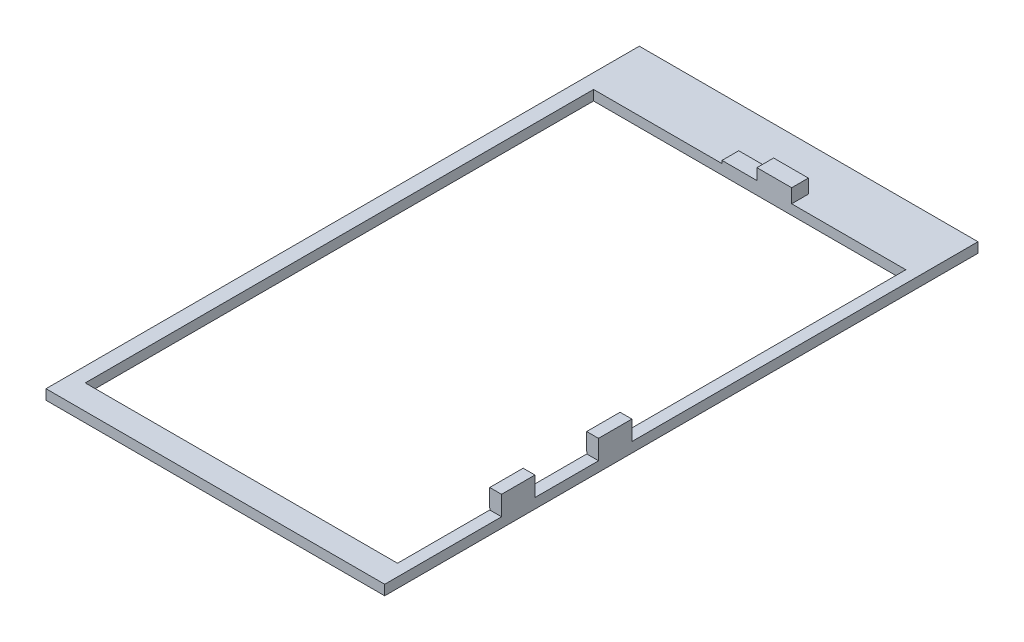
SolidWorks part; units mm, degrees
ref_plane "Front Plane" through (0, 0, 0) normal (0, 0, 1) x (1, 0, 0)
ref_plane "Top Plane" through (0, 0, 0) normal (0, 1, 0) x (1, 0, 0)
ref_plane "Right Plane" through (0, 0, 0) normal (1, 0, 0) x (0, 0, -1)
sketch "Sketch1" plane through (0, 0, 0) normal (0, 1, 0) x (1, 0, 0)
  line L0 (26.2481, 14.4067) -> (26.2382, 20.9067) construction
  line L1 (4.7511, 20.874) -> (16.7382, 20.8922) construction
  line L2 (-0.3474, -87.1339) -> (-0.3459, -88.1339) construction
  line L3 (26.2481, 14.4067) -> (16.7481, 14.3922) construction
  line L4 (26.2481, 14.4067) -> (-0.0019, 14.3667) construction
  line L5 (24.2864, -1.2339) -> (28.4864, -1.2339) construction
  line L6 (26.4026, -87.0932) -> (-27.0974, -87.1746) construction
  line L7 (-27.0974, -87.1746) -> (-27.2518, 14.3252) construction
  line L8 (-27.2518, 14.3252) -> (-0.0019, 14.3667) construction
  line L9 (16.7481, 14.3922) -> (16.7382, 20.8922) construction
  line L10 (4.7614, 14.1135) -> (4.7511, 20.874) construction
  line L16 (-0.3459, -88.1339) -> (29.1041, -88.1339)
  line L22 (29.1041, -88.1339) -> (29.1041, 15.3661)
  line L23 (-0.3459, -88.1339) -> (-28.6959, -88.1339)
  line L24 (-28.6959, -88.1339) -> (-28.6959, 15.3661)
  line L25 (-28.6959, 15.3661) -> (29.1041, 15.3661)
  line L26 (-0.3459, -88.1339) -> (-0.3436, -89.6339) construction
  line L27 (-0.3436, -89.6339) -> (-30.1936, -89.6339)
  line L28 (-0.3436, -89.6339) -> (30.6064, -89.6339)
  line L29 (30.6064, -89.6339) -> (30.6064, 16.8661)
  line L30 (-30.1936, -89.6339) -> (-30.1936, 16.8661)
  line L31 (-30.1936, 16.8661) -> (30.6064, 16.8661)
  line L32 (-23.9736, 0.0361) -> (-23.9736, 6.0361) construction
  line L33 (28.4864, -1.2339) -> (28.4864, 7.1545) construction
  line L34 (-23.9736, 0.0361) -> (-27.5736, 0.0361) construction
  line L35 (-23.9736, 6.0361) -> (28.4864, 6.0361) construction
  line L37 (-27.5736, 6.0361) -> (-23.9736, 6.0361) construction
  line L39 (-27.5736, 6.0361) -> (28.4864, 6.0361)
  line L40 (28.4864, 6.0361) -> (28.4864, -85.2139)
  line L42 (-23.9736, -82.5139) -> (-23.9736, -85.2139) construction
  line L44 (-23.9736, -82.5139) -> (-27.5736, -82.5139) construction
  line L49 (-27.5736, -85.2139) -> (28.4864, -85.2139)
  line L50 (-27.5736, 6.0361) -> (-27.5736, -85.2139)
  circle A8 centre (-23.9736, -82.5139) radius 1.6
  circle A9 centre (24.2864, -76.1639) radius 1.6
  circle A10 centre (24.2864, -1.2339) radius 1.6
  circle A11 centre (-23.9736, 0.0361) radius 1.6
  dimension "D3" = 6
  dimension "D4" = 3.6
  dimension "D6" = 2.7
  dimension "D5" = 4.2
  dimension "D7" = 3.6
  dimension "D9" = 101.5
  dimension "D10" = 53.5
  dimension "D12" = 6.5
  dimension "D13" = 9.5
  dimension "D14" = 1
  dimension "D15" = 29.45
  dimension "D16" = 103.5
  dimension "D17" = 28.35
  dimension "D18" = 1.5
  dimension "D19" = 29.85
  dimension "D20" = 30.95
  dimension "D21" = 106.5
  dimension "D22" = 26.75
extrude "Boss-Extrude1" add sketch "Sketch1" along normal blind 1.8 contours L25 L24 L23 L16 L22 | L31 L30 L27 L28 L29 L24 L25 L22 L16 L23 region at (-14.5209, 0, 86.9485) region at (-15.2686, 0, 88.4076)
sketch "Sketch4" plane through (0, 0, -6.0361) normal (0, 0, 1) x (1, 0, 0)
  line L0 (7.9864, 1.8) -> (7.9864, 4.3)
  line L1 (30.6064, 1.8) -> (-30.1936, 1.8) construction
  line L2 (7.9864, 7.3) -> (7.9864, 1.8) construction
  line L3 (1.7497, 4.3) -> (1.7497, 2.3)
  line L4 (1.7497, 4.3) -> (7.9864, 4.3)
  line L5 (1.7497, 1.8) -> (7.9864, 1.8)
  line L6 (-4.5013, 1.8) -> (-4.5136, 2.3)
  line L7 (-4.5136, 5.5) -> (-4.5136, 1.8) construction
  line L8 (-4.5136, 2.3) -> (1.7497, 2.3)
  line L9 (-4.5013, 1.8) -> (1.7497, 1.8)
  dimension "D1" = 2.5
  dimension "D2" = 0.5
extrude "Boss-Extrude2" add sketch "Sketch4" against normal blind 3
sketch "Sketch5" plane through (30.6064, 0, 0) normal (1, 0, 0) x (0, 0, -1)
  line L0 (-68.6574, 1.8) -> (-68.6639, 5.3)
  line L1 (-89.6339, 1.8) -> (16.8661, 1.8) construction
  line L2 (-68.6639, 8.8) -> (-68.6639, 1.8) construction
  line L3 (-68.6639, 5.3) -> (-62.6639, 5.3)
  line L4 (-62.6639, 5.5) -> (-62.6639, 1.8) construction
  line L5 (-62.6639, 5.3) -> (-62.6639, 1.8)
  line L6 (-62.6639, 1.8) -> (-68.6574, 1.8)
  line L7 (-51.2437, 1.8) -> (-51.2639, 5.3)
  line L8 (-51.2639, 5.5) -> (-51.2639, 1.8) construction
  line L9 (-51.2639, 5.3) -> (-45.2639, 5.3)
  line L10 (-45.2639, 8.8) -> (-45.2639, 1.8) construction
  line L11 (-45.2639, 5.3) -> (-45.2639, 1.8)
  line L12 (-45.2639, 1.8) -> (-51.2437, 1.8)
  dimension "D1" = 3.5
extrude "Boss-Extrude3" add sketch "Sketch5" against normal up to surface (2.12 mm away) up to face at (28.4864, 0.9, 39.5889)
